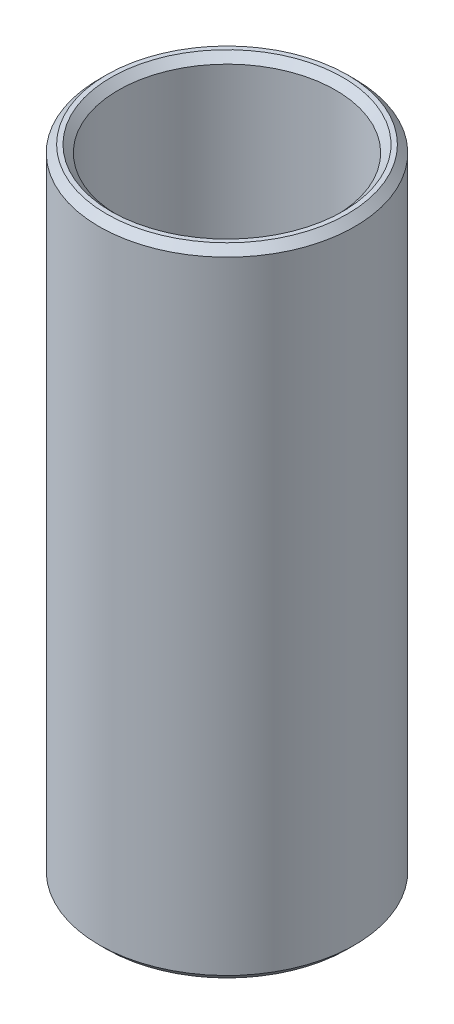
SolidWorks part; units mm, degrees
ref_plane "Front Plane" through (0, 0, 0) normal (0, 0, 1) x (1, 0, 0)
ref_plane "Top Plane" through (0, 0, 0) normal (0, 1, 0) x (1, 0, 0)
ref_plane "Right Plane" through (0, 0, 0) normal (1, 0, 0) x (0, 0, -1)
sketch "Sketch1" plane through (0, 0, 0) normal (0, 1, 0) x (1, 0, 0)
  circle A0 centre (0, 0) radius 55
  dimension "SLEEVE_OD" = 110
extrude "Boss-Extrude1" add sketch "Sketch1" along normal blind 273.944
sketch "Sketch2" plane through (0, 0, 0) normal (0, 1, 0) x (1, 0, 0)
  circle A0 centre (0, 0) radius 46.7608
  dimension "BORE_D" = 93.5217
extrude "Cut-Extrude1" cut sketch "Sketch2" along normal through all
chamfer "Chamfer1" distance 3.1513 angle 45 4 edges at (0, 273.944, 46.7608) (0, 0, 46.7608) (0, 0, 55) (0, 273.944, 55)
